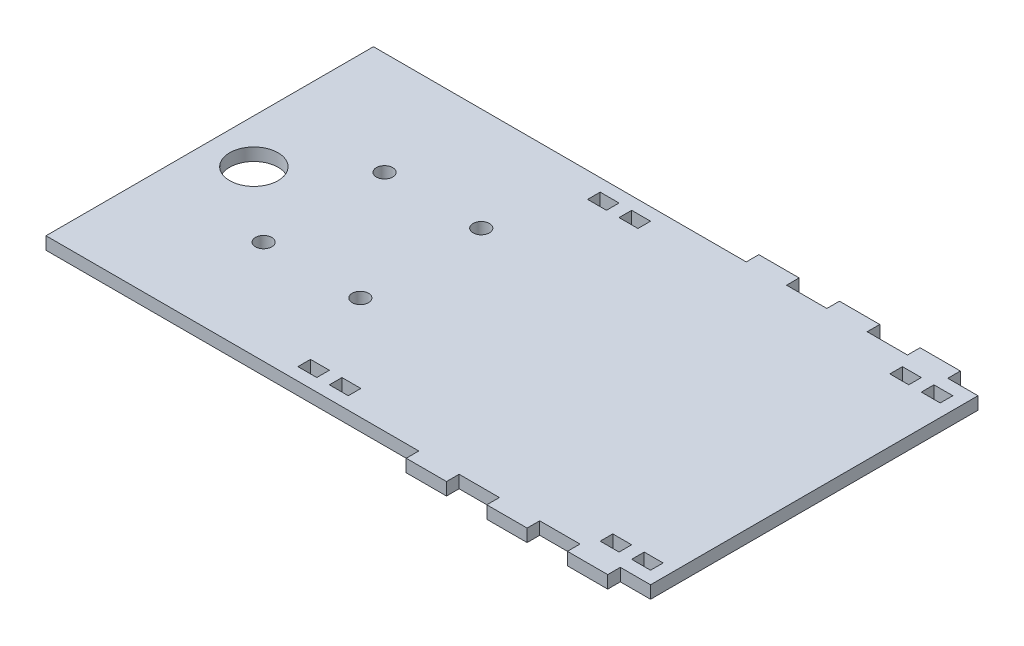
SolidWorks part; units mm, degrees
ref_plane "Front Plane" through (0, 0, 0) normal (0, 0, 1) x (1, 0, 0)
ref_plane "Top Plane" through (0, 0, 0) normal (0, 1, 0) x (1, 0, 0)
ref_plane "Right Plane" through (0, 0, 0) normal (1, 0, 0) x (0, 0, -1)
sketch "Sketch1" plane through (0, 0, 0) normal (0, 1, 0) x (1, 0, 0)
  line L0 (38.1, -41.275) -> (48.26, -41.275)
  line L1 (76.2, -41.275) -> (-76.2, -41.275)
  line L2 (76.2, -41.275) -> (76.2, 41.275)
  line L3 (76.2, 41.275) -> (-76.2, 41.275)
  line L4 (-76.2, -41.275) -> (-76.2, 41.275)
  line L5 (76.2, -41.275) -> (-76.2, 41.275) construction
  line L6 (76.2, 41.275) -> (-76.2, -41.275) construction
  line L7 (58.42, -41.275) -> (68.58, -41.275)
  line L8 (58.42, -41.275) -> (58.42, -44.45)
  line L9 (58.42, -44.45) -> (68.58, -44.45)
  line L10 (68.58, -41.275) -> (68.58, -44.45)
  line L11 (38.1, -41.275) -> (38.1, -44.45)
  line L12 (38.1, -44.45) -> (48.26, -44.45)
  line L13 (48.26, -41.275) -> (48.26, -44.45)
  line L14 (17.78, -41.275) -> (27.94, -41.275)
  line L15 (17.78, -41.275) -> (17.78, -44.45)
  line L16 (17.78, -44.45) -> (27.94, -44.45)
  line L17 (27.94, -41.275) -> (27.94, -44.45)
  line L18 (58.42, 44.45) -> (68.58, 44.45)
  line L19 (58.42, 44.45) -> (58.42, 41.275)
  line L20 (58.42, 41.275) -> (68.58, 41.275)
  line L21 (68.58, 44.45) -> (68.58, 41.275)
  line L22 (38.1, 44.45) -> (48.26, 44.45)
  line L23 (38.1, 44.45) -> (38.1, 41.275)
  line L24 (38.1, 41.275) -> (48.26, 41.275)
  line L25 (48.26, 44.45) -> (48.26, 41.275)
  line L26 (17.78, 44.45) -> (27.94, 44.45)
  line L27 (17.78, 44.45) -> (17.78, 41.275)
  line L28 (17.78, 41.275) -> (27.94, 41.275)
  line L29 (27.94, 44.45) -> (27.94, 41.275)
  line L30 (58.42, -41.275) -> (38.1, -41.275) construction
  circle A0 centre (-65.0766, 0) radius 6.096
  point P0 (0, 0)
  dimension "D9" = 12.192
  dimension "D1" = 3.175
  dimension "D2" = 10.16
  dimension "D5" = 20.32
  dimension "D6" = 82.55
  dimension "D7" = 152.4
  dimension "D8" = 7.62
  dimension "D3" = 3
  dimension "D4" = 2
extrude "Boss-Extrude1" add sketch "Sketch1" along normal blind 3.175 contours L17 L1 L15 L16 | L4 L1 L0 L2 L3 | L13 L0 L11 L12 | L29 L26 L27 L3 | L10 L9 L8 L7 | L18 L21 L20 L19 | L22 L25 L24 L23 region at (0.6096, 0, 0) region at (43.18, 0, 42.8625) region at (22.86, 0, 42.8625) region at (22.86, 0, -42.8625)
sketch "Sketch2" plane through (0, 3.175, 0) normal (0, 1, 0) x (1, 0, 0)
  line L0 (-47.3754, 15.24) -> (-47.3754, -15.24) construction
  line L1 (-47.3754, 0) -> (-76.2, 0) construction
  line L2 (-76.2, -41.275) -> (-76.2, 41.275) construction
  circle A0 centre (-47.3754, 15.24) radius 2.0638
  circle A1 centre (-22.9914, 15.24) radius 2.0638
  circle A2 centre (-22.9914, -15.24) radius 2.0638
  circle A3 centre (-47.3754, -15.24) radius 2.0638
  dimension "D4" = 24.384
  dimension "D5" = 4.1275
  dimension "D3" = 30.48
  dimension "D1" = 2
  dimension "D2" = 2
extrude "Caster Mounting Holes" cut sketch "Sketch2" against normal through all
sketch "Sketch3" plane through (0, 3.175, 0) normal (0, 1, 0) x (1, 0, 0)
  line L0 (58.42, 41.275) -> (48.26, 41.275) construction
  line L2 (65.0875, 38.1) -> (65.0875, 34.925)
  line L4 (68.2625, 38.1) -> (68.2625, 34.925)
  line L7 (76.2, -41.275) -> (76.2, 41.275) construction
  line L9 (68.2625, 38.1) -> (73.025, 38.1)
  line L10 (73.025, 38.1) -> (73.025, 34.925)
  line L11 (73.025, 34.925) -> (68.2625, 34.925)
  line L15 (65.0875, 34.925) -> (60.325, 34.925)
  line L16 (60.325, 34.925) -> (60.325, 38.1)
  line L17 (60.325, 38.1) -> (65.0875, 38.1)
  point P0 (66.675, 36.5125)
  dimension "D1" = 3.175
  dimension "D2" = 4.7625
  dimension "D3" = 3.175
  dimension "D4" = 3.175
  dimension "D5" = 3.175
extrude "Cut-Extrude1" cut sketch "Sketch3" against normal through all contours L17 L16 L15 L2 | L11 L10 L9 L4 region at (62.7063, 3.175, -36.5125) region at (70.6438, 3.175, -36.5125)
pattern_linear "LPattern1" count 2 spacing 76.2 along (-1, 0, 0) count 2 spacing 73.025 along (0, 0, 1) of "Cut-Extrude1"
sketch "Sketch4" plane through (0, 3.175, 0) normal (0, 1, 0) x (1, 0, 0)
  line L9 (-11.1887, -38.0238) -> (-11.1887, -35.0012)
  line L10 (-15.7988, -38.0238) -> (-11.1887, -38.0238)
  line L11 (-15.7988, -35.0012) -> (-15.7988, -38.0238)
  line L12 (-11.1887, -35.0012) -> (-15.7988, -35.0012)
  line L13 (-11.1887, -38.0238) -> (-11.1887, -35.0012)
  line L14 (-15.7988, -38.0238) -> (-11.1887, -38.0238)
  line L15 (-15.7988, -35.0012) -> (-15.7988, -38.0238)
  line L16 (-11.1887, -35.0012) -> (-15.7988, -35.0012)
  line L21 (-3.2512, -38.0238) -> (-3.2512, -35.0012)
  line L22 (-3.2512, -35.0012) -> (-7.8613, -35.0012)
  line L23 (-7.8613, -35.0012) -> (-7.8613, -38.0238)
  line L24 (-7.8613, -38.0238) -> (-3.2512, -38.0238)
  line L25 (-3.2512, -38.0238) -> (-3.2512, -35.0012)
  line L26 (-3.2512, -35.0012) -> (-7.8613, -35.0012)
  line L27 (-7.8613, -35.0012) -> (-7.8613, -38.0238)
  line L28 (-7.8613, -38.0238) -> (-3.2512, -38.0238)
  line L33 (60.4012, -38.0238) -> (65.0113, -38.0238)
  line L34 (60.4012, -35.0012) -> (60.4012, -38.0238)
  line L35 (65.0113, -35.0012) -> (60.4012, -35.0012)
  line L36 (65.0113, -38.0238) -> (65.0113, -35.0012)
  line L37 (60.4012, -38.0238) -> (65.0113, -38.0238)
  line L38 (60.4012, -35.0012) -> (60.4012, -38.0238)
  line L39 (65.0113, -35.0012) -> (60.4012, -35.0012)
  line L40 (65.0113, -38.0238) -> (65.0113, -35.0012)
  line L45 (72.9488, -35.0012) -> (68.3387, -35.0012)
  line L46 (68.3387, -35.0012) -> (68.3387, -38.0238)
  line L47 (72.9488, -38.0238) -> (72.9488, -35.0012)
  line L48 (68.3387, -38.0238) -> (72.9488, -38.0238)
  line L49 (72.9488, -35.0012) -> (68.3387, -35.0012)
  line L50 (68.3387, -35.0012) -> (68.3387, -38.0238)
  line L51 (72.9488, -38.0238) -> (72.9488, -35.0012)
  line L52 (68.3387, -38.0238) -> (72.9488, -38.0238)
  line L57 (65.0113, 35.0012) -> (65.0113, 38.0238)
  line L58 (65.0113, 38.0238) -> (60.4012, 38.0238)
  line L59 (60.4012, 38.0238) -> (60.4012, 35.0012)
  line L60 (60.4012, 35.0012) -> (65.0113, 35.0012)
  line L61 (65.0113, 35.0012) -> (65.0113, 38.0238)
  line L62 (65.0113, 38.0238) -> (60.4012, 38.0238)
  line L63 (60.4012, 38.0238) -> (60.4012, 35.0012)
  line L64 (60.4012, 35.0012) -> (65.0113, 35.0012)
  line L69 (72.9488, 35.0012) -> (72.9488, 38.0238)
  line L70 (72.9488, 38.0238) -> (68.3387, 38.0238)
  line L71 (68.3387, 38.0238) -> (68.3387, 35.0012)
  line L72 (68.3387, 35.0012) -> (72.9488, 35.0012)
  line L73 (72.9488, 35.0012) -> (72.9488, 38.0238)
  line L74 (72.9488, 38.0238) -> (68.3387, 38.0238)
  line L75 (68.3387, 38.0238) -> (68.3387, 35.0012)
  line L76 (68.3387, 35.0012) -> (72.9488, 35.0012)
  line L81 (-7.8613, 38.0238) -> (-7.8613, 35.0012)
  line L82 (-3.2512, 38.0238) -> (-7.8613, 38.0238)
  line L83 (-3.2512, 35.0012) -> (-3.2512, 38.0238)
  line L84 (-7.8613, 35.0012) -> (-3.2512, 35.0012)
  line L85 (-7.8613, 38.0238) -> (-7.8613, 35.0012)
  line L86 (-3.2512, 38.0238) -> (-7.8613, 38.0238)
  line L87 (-3.2512, 35.0012) -> (-3.2512, 38.0238)
  line L88 (-7.8613, 35.0012) -> (-3.2512, 35.0012)
  line L93 (-15.7988, 38.0238) -> (-15.7988, 35.0012)
  line L94 (-11.1887, 38.0238) -> (-15.7988, 38.0238)
  line L95 (-11.1887, 35.0012) -> (-11.1887, 38.0238)
  line L96 (-15.7988, 35.0012) -> (-11.1887, 35.0012)
  line L97 (-15.7988, 38.0238) -> (-15.7988, 35.0012)
  line L98 (-11.1887, 38.0238) -> (-15.7988, 38.0238)
  line L99 (-11.1887, 35.0012) -> (-11.1887, 38.0238)
  line L100 (-15.7988, 35.0012) -> (-11.1887, 35.0012)
  line L455 (17.7038, 44.5262) -> (17.7038, 41.3512)
  line L456 (28.0162, 44.5262) -> (17.7038, 44.5262)
  line L457 (28.0162, 41.3512) -> (28.0162, 44.5262)
  line L458 (38.0238, 41.3512) -> (28.0162, 41.3512)
  line L459 (38.0238, 44.5262) -> (38.0238, 41.3512)
  line L460 (48.3362, 44.5262) -> (38.0238, 44.5262)
  line L461 (48.3362, 41.3512) -> (48.3362, 44.5262)
  line L462 (58.3438, 41.3512) -> (48.3362, 41.3512)
  line L463 (58.3438, 44.5262) -> (58.3438, 41.3512)
  line L464 (68.6562, 44.5262) -> (58.3438, 44.5262)
  line L465 (68.6562, 41.3512) -> (68.6562, 44.5262)
  line L466 (76.2762, 41.3512) -> (68.6562, 41.3512)
  line L467 (68.6562, -41.3512) -> (76.2762, -41.3512)
  line L468 (68.6562, -44.5262) -> (68.6562, -41.3512)
  line L469 (58.3438, -44.5262) -> (68.6562, -44.5262)
  line L470 (58.3438, -41.3512) -> (58.3438, -44.5262)
  line L471 (48.3362, -41.3512) -> (58.3438, -41.3512)
  line L472 (48.3362, -44.5262) -> (48.3362, -41.3512)
  line L473 (38.0238, -44.5262) -> (48.3362, -44.5262)
  line L474 (38.0238, -41.3512) -> (38.0238, -44.5262)
  line L475 (28.0162, -41.3512) -> (38.0238, -41.3512)
  line L476 (28.0162, -44.5262) -> (28.0162, -41.3512)
  line L477 (17.7038, -44.5262) -> (28.0162, -44.5262)
  line L478 (17.7038, -41.3512) -> (17.7038, -44.5262)
  line L479 (76.2762, -41.3512) -> (76.2762, 41.3512)
  line L480 (-76.2762, -41.3512) -> (17.7038, -41.3512)
  line L481 (17.7038, 41.3512) -> (-76.2762, 41.3512)
  line L482 (-76.2762, 41.3512) -> (-76.2762, -41.3512)
  line L483 (17.7038, 44.5262) -> (17.7038, 41.3512)
  line L484 (28.0162, 44.5262) -> (17.7038, 44.5262)
  line L485 (28.0162, 41.3512) -> (28.0162, 44.5262)
  line L486 (38.0238, 41.3512) -> (28.0162, 41.3512)
  line L487 (38.0238, 44.5262) -> (38.0238, 41.3512)
  line L488 (48.3362, 44.5262) -> (38.0238, 44.5262)
  line L489 (48.3362, 41.3512) -> (48.3362, 44.5262)
  line L490 (58.3438, 41.3512) -> (48.3362, 41.3512)
  line L491 (58.3438, 44.5262) -> (58.3438, 41.3512)
  line L492 (68.6562, 44.5262) -> (58.3438, 44.5262)
  line L493 (68.6562, 41.3512) -> (68.6562, 44.5262)
  line L494 (76.2762, 41.3512) -> (68.6562, 41.3512)
  line L495 (68.6562, -41.3512) -> (76.2762, -41.3512)
  line L496 (68.6562, -44.5262) -> (68.6562, -41.3512)
  line L497 (58.3438, -44.5262) -> (68.6562, -44.5262)
  line L498 (58.3438, -41.3512) -> (58.3438, -44.5262)
  line L499 (48.3362, -41.3512) -> (58.3438, -41.3512)
  line L500 (48.3362, -44.5262) -> (48.3362, -41.3512)
  line L501 (38.0238, -44.5262) -> (48.3362, -44.5262)
  line L502 (38.0238, -41.3512) -> (38.0238, -44.5262)
  line L503 (28.0162, -41.3512) -> (38.0238, -41.3512)
  line L504 (28.0162, -44.5262) -> (28.0162, -41.3512)
  line L505 (17.7038, -44.5262) -> (28.0162, -44.5262)
  line L506 (17.7038, -41.3512) -> (17.7038, -44.5262)
  line L507 (76.2762, -41.3512) -> (76.2762, 41.3512)
  line L508 (-76.2762, -41.3512) -> (17.7038, -41.3512)
  line L509 (17.7038, 41.3512) -> (-76.2762, 41.3512)
  line L510 (-76.2762, 41.3512) -> (-76.2762, -41.3512)
  circle A2 centre (-47.3754, -15.24) radius 1.9876
  circle A3 centre (-47.3754, -15.24) radius 1.9876
  circle A4 centre (-65.0766, 0) radius 6.0198
  circle A5 centre (-47.3754, 15.24) radius 1.9876
  circle A6 centre (-47.3754, 15.24) radius 1.9876
  circle A7 centre (-65.0766, 0) radius 6.0198
  circle A8 centre (-22.9914, 15.24) radius 1.9876
  circle A9 centre (-22.9914, 15.24) radius 1.9876
  circle A11 centre (-22.9914, -15.24) radius 1.9876
  circle A12 centre (-22.9914, -15.24) radius 1.9876
  dimension "D1" = 0.0762
  dimension "D2" = 0.0762
  dimension "D3" = 0.0762
  dimension "D4" = 0.0762
  dimension "D5" = 0.0762
  dimension "D6" = 0.0762
  dimension "D7" = 0.0762
  dimension "D8" = 0.0762
  dimension "D9" = 0.0762
  dimension "D10" = 0.0762
  dimension "D11" = 0.0762
  dimension "D12" = 0.0762
  dimension "D13" = 0.0762
  dimension "D14" = 0.0762
